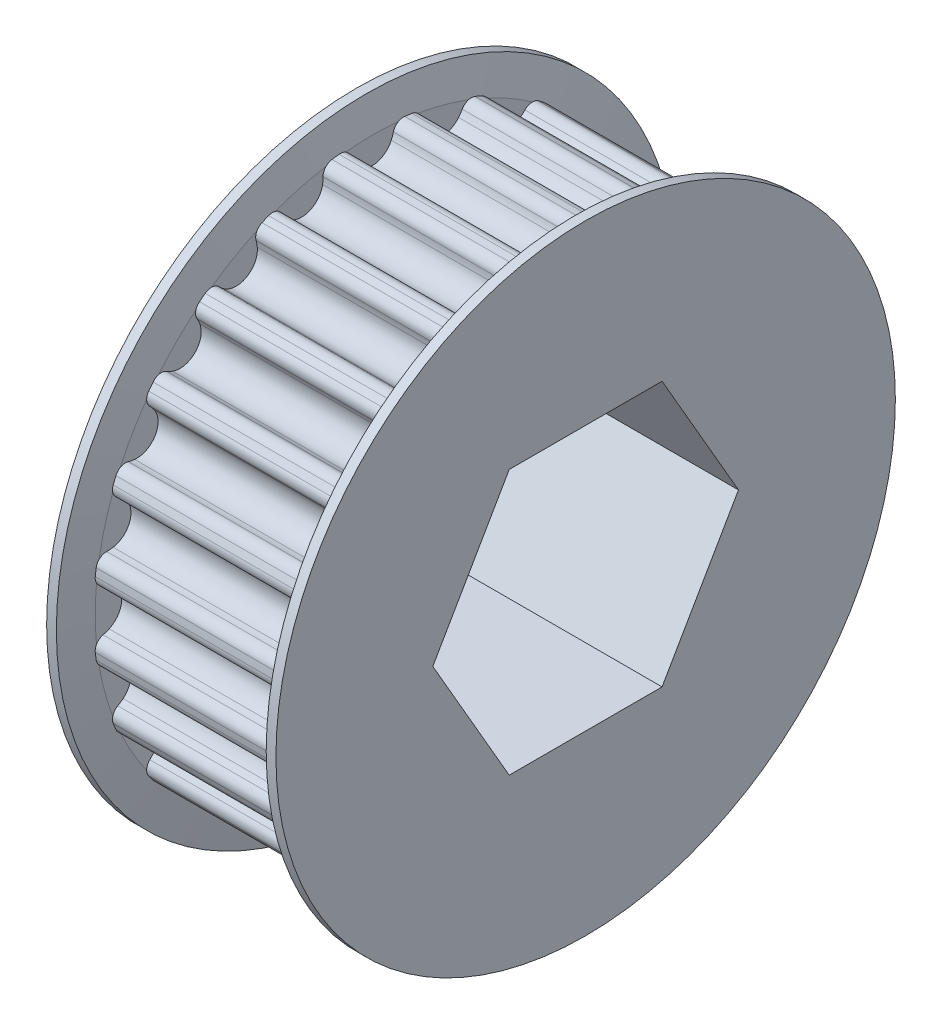
SolidWorks part; units mm, degrees
material "PET"
ref_plane "Front" through (0, 0, 0) normal (0, 0, 1) x (1, 0, 0)
ref_plane "Top" through (0, 0, 0) normal (0, 1, 0) x (1, 0, 0)
ref_plane "Right" through (0, 0, 0) normal (1, 0, 0) x (0, 0, -1)
sketch "Sketch1" plane through (0, 0, 0) normal (1, 0, 0) x (0, 0, -1)
  arc A0 (5.5576, 11.6856) -> (5.2736, 12.2806) centre (5.0763, 11.8212) ccw
  arc A1 (5.2736, 12.2806) -> (4.9547, 12.4127) centre (0, 0) ccw
  arc A2 (4.9547, 12.4127) -> (4.3332, 12.1928) centre (4.7694, 11.9483) ccw
  arc A3 (4.1589, 11.936) -> (4.3332, 12.1928) centre (2.7488, 13.0808) ccw
  arc A4 (2.3663, 12.4163) -> (4.1589, 11.936) centre (3.3699, 12.5766) ccw
  arc A5 (2.3437, 12.7258) -> (2.3663, 12.4163) centre (4.1598, 12.7027) ccw
  arc A6 (2.3437, 12.7258) -> (1.9154, 13.2271) centre (1.8438, 12.7322) ccw
  arc A7 (1.9154, 13.2271) -> (1.5733, 13.2721) centre (0, 0) ccw
  arc A8 (1.5733, 13.2721) -> (1.0298, 12.8988) centre (1.5144, 12.7756) ccw
  arc A9 (0.9279, 12.6057) -> (1.0298, 12.8988) centre (-0.7304, 13.3465) ccw
  arc A10 (-0.9279, 12.6057) -> (0.9279, 12.6057) centre (0, 13.0202) ccw
  arc A11 (-1.0298, 12.8988) -> (-0.9279, 12.6057) centre (0.7304, 13.3465) ccw
  arc A12 (-1.0298, 12.8988) -> (-1.5733, 13.2721) centre (-1.5144, 12.7756) ccw
  arc A13 (-1.5733, 13.2721) -> (-1.9154, 13.2271) centre (0, 0) ccw
  arc A14 (-1.9154, 13.2271) -> (-2.3437, 12.7258) centre (-1.8438, 12.7322) ccw
  arc A15 (-2.3663, 12.4163) -> (-2.3437, 12.7258) centre (-4.1598, 12.7027) ccw
  arc A16 (-4.1589, 11.936) -> (-2.3663, 12.4163) centre (-3.3699, 12.5766) ccw
  arc A17 (-4.3332, 12.1928) -> (-4.1589, 11.936) centre (-2.7488, 13.0808) ccw
  arc A18 (-4.3332, 12.1928) -> (-4.9547, 12.4127) centre (-4.7694, 11.9483) ccw
  arc A19 (-4.9547, 12.4127) -> (-5.2736, 12.2806) centre (0, 0) ccw
  arc A20 (-5.2736, 12.2806) -> (-5.5576, 11.6856) centre (-5.0763, 11.8212) ccw
  arc A21 (-5.4993, 11.3808) -> (-5.5576, 11.6856) centre (-7.3058, 11.1932) ccw
  arc A22 (-7.1064, 10.4529) -> (-5.4993, 11.3808) centre (-6.5101, 11.2758) ccw
  arc A23 (-7.3413, 10.6558) -> (-7.1064, 10.4529) centre (-6.0407, 11.9236) ccw
  arc A24 (-7.3413, 10.6558) -> (-7.9986, 10.7074) centre (-7.6993, 10.3068) ccw
  arc A25 (-7.9986, 10.7074) -> (-8.2723, 10.4973) centre (0, 0) ccw
  arc A26 (-8.2723, 10.4973) -> (-8.3927, 9.849) centre (-7.9628, 10.1045) ccw
  arc A27 (-8.2575, 9.5697) -> (-8.3927, 9.849) centre (-9.9539, 8.9209) ccw
  arc A28 (-9.5697, 8.2575) -> (-8.2575, 9.5697) centre (-9.2067, 9.2067) ccw
  arc A29 (-9.849, 8.3927) -> (-9.5697, 8.2575) centre (-8.9209, 9.9539) ccw
  arc A30 (-9.849, 8.3927) -> (-10.4973, 8.2723) centre (-10.1045, 7.9628) ccw
  arc A31 (-10.4973, 8.2723) -> (-10.7074, 7.9986) centre (0, 0) ccw
  arc A32 (-10.7074, 7.9986) -> (-10.6558, 7.3413) centre (-10.3068, 7.6993) ccw
  arc A33 (-10.4529, 7.1064) -> (-10.6558, 7.3413) centre (-11.9236, 6.0407) ccw
  arc A34 (-11.3808, 5.4993) -> (-10.4529, 7.1064) centre (-11.2758, 6.5101) ccw
  arc A35 (-11.6856, 5.5576) -> (-11.3808, 5.4993) centre (-11.1932, 7.3058) ccw
  arc A36 (-11.6856, 5.5576) -> (-12.2806, 5.2736) centre (-11.8212, 5.0763) ccw
  arc A37 (-12.2806, 5.2736) -> (-12.4127, 4.9547) centre (0, 0) ccw
  arc A38 (-12.4127, 4.9547) -> (-12.1928, 4.3332) centre (-11.9483, 4.7694) ccw
  arc A39 (-11.936, 4.1589) -> (-12.1928, 4.3332) centre (-13.0808, 2.7488) ccw
  arc A40 (-12.4163, 2.3663) -> (-11.936, 4.1589) centre (-12.5766, 3.3699) ccw
  arc A41 (-12.7258, 2.3437) -> (-12.4163, 2.3663) centre (-12.7027, 4.1598) ccw
  arc A42 (-12.7258, 2.3437) -> (-13.2271, 1.9154) centre (-12.7322, 1.8438) ccw
  arc A43 (-13.2271, 1.9154) -> (-13.2721, 1.5733) centre (0, 0) ccw
  arc A44 (-13.2721, 1.5733) -> (-12.8988, 1.0298) centre (-12.7756, 1.5144) ccw
  arc A45 (-12.6057, 0.9279) -> (-12.8988, 1.0298) centre (-13.3465, -0.7304) ccw
  arc A46 (-12.6057, -0.9279) -> (-12.6057, 0.9279) centre (-13.0202, 0) ccw
  arc A47 (-12.8988, -1.0298) -> (-12.6057, -0.9279) centre (-13.3465, 0.7304) ccw
  arc A48 (-12.8988, -1.0298) -> (-13.2721, -1.5733) centre (-12.7756, -1.5144) ccw
  arc A49 (-13.2721, -1.5733) -> (-13.2271, -1.9154) centre (0, 0) ccw
  arc A50 (-13.2271, -1.9154) -> (-12.7258, -2.3437) centre (-12.7322, -1.8438) ccw
  arc A51 (-12.4163, -2.3663) -> (-12.7258, -2.3437) centre (-12.7027, -4.1598) ccw
  arc A52 (-11.936, -4.1589) -> (-12.4163, -2.3663) centre (-12.5766, -3.3699) ccw
  arc A53 (-12.1928, -4.3332) -> (-11.936, -4.1589) centre (-13.0808, -2.7488) ccw
  arc A54 (-12.1928, -4.3332) -> (-12.4127, -4.9547) centre (-11.9483, -4.7694) ccw
  arc A55 (-12.4127, -4.9547) -> (-12.2806, -5.2736) centre (0, 0) ccw
  arc A56 (-12.2806, -5.2736) -> (-11.6856, -5.5576) centre (-11.8212, -5.0763) ccw
  arc A57 (-11.3808, -5.4993) -> (-11.6856, -5.5576) centre (-11.1932, -7.3058) ccw
  arc A58 (-10.4529, -7.1064) -> (-11.3808, -5.4993) centre (-11.2758, -6.5101) ccw
  arc A59 (-10.6558, -7.3413) -> (-10.4529, -7.1064) centre (-11.9236, -6.0407) ccw
  arc A60 (-10.6558, -7.3413) -> (-10.7074, -7.9986) centre (-10.3068, -7.6993) ccw
  arc A61 (-10.7074, -7.9986) -> (-10.4973, -8.2723) centre (0, 0) ccw
  arc A62 (-10.4973, -8.2723) -> (-9.849, -8.3927) centre (-10.1045, -7.9628) ccw
  arc A63 (-9.5697, -8.2575) -> (-9.849, -8.3927) centre (-8.9209, -9.9539) ccw
  arc A64 (-8.2575, -9.5697) -> (-9.5697, -8.2575) centre (-9.2067, -9.2067) ccw
  arc A65 (-8.3927, -9.849) -> (-8.2575, -9.5697) centre (-9.9539, -8.9209) ccw
  arc A66 (-8.3927, -9.849) -> (-8.2723, -10.4973) centre (-7.9628, -10.1045) ccw
  arc A67 (-8.2723, -10.4973) -> (-7.9986, -10.7074) centre (0, 0) ccw
  arc A68 (-7.9986, -10.7074) -> (-7.3413, -10.6558) centre (-7.6993, -10.3068) ccw
  arc A69 (-7.1064, -10.4529) -> (-7.3413, -10.6558) centre (-6.0407, -11.9236) ccw
  arc A70 (-5.4993, -11.3808) -> (-7.1064, -10.4529) centre (-6.5101, -11.2758) ccw
  arc A71 (-5.5576, -11.6856) -> (-5.4993, -11.3808) centre (-7.3058, -11.1932) ccw
  arc A72 (-5.5576, -11.6856) -> (-5.2736, -12.2806) centre (-5.0763, -11.8212) ccw
  arc A73 (-5.2736, -12.2806) -> (-4.9547, -12.4127) centre (0, 0) ccw
  arc A74 (-4.9547, -12.4127) -> (-4.3332, -12.1928) centre (-4.7694, -11.9483) ccw
  arc A75 (-4.1589, -11.936) -> (-4.3332, -12.1928) centre (-2.7488, -13.0808) ccw
  arc A76 (-2.3663, -12.4163) -> (-4.1589, -11.936) centre (-3.3699, -12.5766) ccw
  arc A77 (-2.3437, -12.7258) -> (-2.3663, -12.4163) centre (-4.1598, -12.7027) ccw
  arc A78 (-2.3437, -12.7258) -> (-1.9154, -13.2271) centre (-1.8438, -12.7322) ccw
  arc A79 (-1.9154, -13.2271) -> (-1.5733, -13.2721) centre (0, 0) ccw
  arc A80 (-1.5733, -13.2721) -> (-1.0298, -12.8988) centre (-1.5144, -12.7756) ccw
  arc A81 (-0.9279, -12.6057) -> (-1.0298, -12.8988) centre (0.7304, -13.3465) ccw
  arc A82 (0.9279, -12.6057) -> (-0.9279, -12.6057) centre (0, -13.0202) ccw
  arc A83 (1.0298, -12.8988) -> (0.9279, -12.6057) centre (-0.7304, -13.3465) ccw
  arc A84 (1.0298, -12.8988) -> (1.5733, -13.2721) centre (1.5144, -12.7756) ccw
  arc A85 (1.5733, -13.2721) -> (1.9154, -13.2271) centre (0, 0) ccw
  arc A86 (1.9154, -13.2271) -> (2.3437, -12.7258) centre (1.8438, -12.7322) ccw
  arc A87 (2.3663, -12.4163) -> (2.3437, -12.7258) centre (4.1598, -12.7027) ccw
  arc A88 (4.1589, -11.936) -> (2.3663, -12.4163) centre (3.3699, -12.5766) ccw
  arc A89 (4.3332, -12.1928) -> (4.1589, -11.936) centre (2.7488, -13.0808) ccw
  arc A90 (4.3332, -12.1928) -> (4.9547, -12.4127) centre (4.7694, -11.9483) ccw
  arc A91 (4.9547, -12.4127) -> (5.2736, -12.2806) centre (0, 0) ccw
  arc A92 (5.2736, -12.2806) -> (5.5576, -11.6856) centre (5.0763, -11.8212) ccw
  arc A93 (5.4993, -11.3808) -> (5.5576, -11.6856) centre (7.3058, -11.1932) ccw
  arc A94 (7.1064, -10.4529) -> (5.4993, -11.3808) centre (6.5101, -11.2758) ccw
  arc A95 (7.3413, -10.6558) -> (7.1064, -10.4529) centre (6.0407, -11.9236) ccw
  arc A96 (7.3413, -10.6558) -> (7.9986, -10.7074) centre (7.6993, -10.3068) ccw
  arc A97 (7.9986, -10.7074) -> (8.2723, -10.4973) centre (0, 0) ccw
  arc A98 (8.2723, -10.4973) -> (8.3927, -9.849) centre (7.9628, -10.1045) ccw
  arc A99 (8.2575, -9.5697) -> (8.3927, -9.849) centre (9.9539, -8.9209) ccw
  arc A100 (9.5697, -8.2575) -> (8.2575, -9.5697) centre (9.2067, -9.2067) ccw
  arc A101 (9.849, -8.3927) -> (9.5697, -8.2575) centre (8.9209, -9.9539) ccw
  arc A102 (9.849, -8.3927) -> (10.4973, -8.2723) centre (10.1045, -7.9628) ccw
  arc A103 (10.4973, -8.2723) -> (10.7074, -7.9986) centre (0, 0) ccw
  arc A104 (10.7074, -7.9986) -> (10.6558, -7.3413) centre (10.3068, -7.6993) ccw
  arc A105 (10.4529, -7.1064) -> (10.6558, -7.3413) centre (11.9236, -6.0407) ccw
  arc A106 (11.3808, -5.4993) -> (10.4529, -7.1064) centre (11.2758, -6.5101) ccw
  arc A107 (11.6856, -5.5576) -> (11.3808, -5.4993) centre (11.1932, -7.3058) ccw
  arc A108 (11.6856, -5.5576) -> (12.2806, -5.2736) centre (11.8212, -5.0763) ccw
  arc A109 (12.2806, -5.2736) -> (12.4127, -4.9547) centre (0, 0) ccw
  arc A110 (12.4127, -4.9547) -> (12.1928, -4.3332) centre (11.9483, -4.7694) ccw
  arc A111 (11.936, -4.1589) -> (12.1928, -4.3332) centre (13.0808, -2.7488) ccw
  arc A112 (12.4163, -2.3663) -> (11.936, -4.1589) centre (12.5766, -3.3699) ccw
  arc A113 (12.7258, -2.3437) -> (12.4163, -2.3663) centre (12.7027, -4.1598) ccw
  arc A114 (12.7258, -2.3437) -> (13.2271, -1.9154) centre (12.7322, -1.8438) ccw
  arc A115 (13.2271, -1.9154) -> (13.2721, -1.5733) centre (0, 0) ccw
  arc A116 (13.2721, -1.5733) -> (12.8988, -1.0298) centre (12.7756, -1.5144) ccw
  arc A117 (12.6057, -0.9279) -> (12.8988, -1.0298) centre (13.3465, 0.7304) ccw
  arc A118 (12.6057, 0.9279) -> (12.6057, -0.9279) centre (13.0202, 0) ccw
  arc A119 (12.8988, 1.0298) -> (12.6057, 0.9279) centre (13.3465, -0.7304) ccw
  arc A120 (12.8988, 1.0298) -> (13.2721, 1.5733) centre (12.7756, 1.5144) ccw
  arc A121 (13.2721, 1.5733) -> (13.2271, 1.9154) centre (0, 0) ccw
  arc A122 (13.2271, 1.9154) -> (12.7258, 2.3437) centre (12.7322, 1.8438) ccw
  arc A123 (12.4163, 2.3663) -> (12.7258, 2.3437) centre (12.7027, 4.1598) ccw
  arc A124 (11.936, 4.1589) -> (12.4163, 2.3663) centre (12.5766, 3.3699) ccw
  arc A125 (12.1928, 4.3332) -> (11.936, 4.1589) centre (13.0808, 2.7488) ccw
  arc A126 (12.1928, 4.3332) -> (12.4127, 4.9547) centre (11.9483, 4.7694) ccw
  arc A127 (12.4127, 4.9547) -> (12.2806, 5.2736) centre (0, 0) ccw
  arc A128 (12.2806, 5.2736) -> (11.6856, 5.5576) centre (11.8212, 5.0763) ccw
  arc A129 (11.3808, 5.4993) -> (11.6856, 5.5576) centre (11.1932, 7.3058) ccw
  arc A130 (10.4529, 7.1064) -> (11.3808, 5.4993) centre (11.2758, 6.5101) ccw
  arc A131 (10.6558, 7.3413) -> (10.4529, 7.1064) centre (11.9236, 6.0407) ccw
  arc A132 (10.6558, 7.3413) -> (10.7074, 7.9986) centre (10.3068, 7.6993) ccw
  arc A133 (10.7074, 7.9986) -> (10.4973, 8.2723) centre (0, 0) ccw
  arc A134 (10.4973, 8.2723) -> (9.849, 8.3927) centre (10.1045, 7.9628) ccw
  arc A135 (9.5697, 8.2575) -> (9.849, 8.3927) centre (8.9209, 9.9539) ccw
  arc A136 (8.2575, 9.5697) -> (9.5697, 8.2575) centre (9.2067, 9.2067) ccw
  arc A137 (8.3927, 9.849) -> (8.2575, 9.5697) centre (9.9539, 8.9209) ccw
  arc A138 (8.3927, 9.849) -> (8.2723, 10.4973) centre (7.9628, 10.1045) ccw
  arc A139 (8.2723, 10.4973) -> (7.9986, 10.7074) centre (0, 0) ccw
  arc A140 (7.9986, 10.7074) -> (7.3413, 10.6558) centre (7.6993, 10.3068) ccw
  arc A141 (7.1064, 10.4529) -> (7.3413, 10.6558) centre (6.0407, 11.9236) ccw
  arc A142 (5.4993, 11.3808) -> (7.1064, 10.4529) centre (6.5101, 11.2758) ccw
  arc A143 (5.5576, 11.6856) -> (5.4993, 11.3808) centre (7.3058, 11.1932) ccw
extrude "Boss-Extrude1" add sketch "Sketch1" along normal mid plane 9.508
sketch "Sketch2" plane through (0, 0, 0) normal (0, 0, 1) x (1, 0, 0)
  line L0 (-8.3357, 0) -> (8.3357, 0) construction
  line L1 (4.754, 13.2721) -> (-4.754, 13.2721) construction
  line L2 (-5.5, 4.7625) -> (-4.754, 4.7625)
  line L3 (-4.754, 4.7625) -> (-4.754, 13.2721)
  line L4 (-4.754, 13.2721) -> (-5.0339, 14.8596)
  line L5 (-5.0339, 14.8596) -> (-5.5, 14.8596)
  line L6 (-5.5, 14.8596) -> (-5.5, 4.7625)
  line L7 (-4.754, 11.6856) -> (-4.754, 11.3808) construction
  line L8 (0, 0) -> (0, 16.7777) construction
  line L9 (5.5, 14.8596) -> (5.5, 4.7625)
  line L10 (5.0339, 14.8596) -> (5.5, 14.8596)
  line L11 (4.754, 13.2721) -> (5.0339, 14.8596)
  line L12 (4.754, 4.7625) -> (4.754, 13.2721)
  line L13 (5.5, 4.7625) -> (4.754, 4.7625)
  point P3 (-4.754, 13.2721)
  point P4 (0, 0)
  dimension "D1" = 4.7625
  dimension "D2" = 0.746
  dimension "D4" = 1.5875
  dimension "D5" = 100
revolve "Revolve1" add sketch "Sketch2" angle 360 about L0
sketch "Sketch3" plane through (0, 0, 0) normal (1, 0, 0) x (0, 0, -1)
  line L1 (7.3323, 0) -> (3.6662, 6.35)
  line L2 (3.6662, 6.35) -> (-3.6662, 6.35)
  line L3 (-3.6662, 6.35) -> (-7.3323, 0)
  line L4 (-7.3323, 0) -> (-3.6662, -6.35)
  line L5 (-3.6662, -6.35) -> (3.6662, -6.35)
  line L6 (3.6662, -6.35) -> (7.3323, 0)
  circle A0 centre (0, 0) radius 6.35 construction
  dimension "D1" = 12.7
extrude "Cut-Extrude1" cut sketch "Sketch3" against normal through all both and the other way through all
